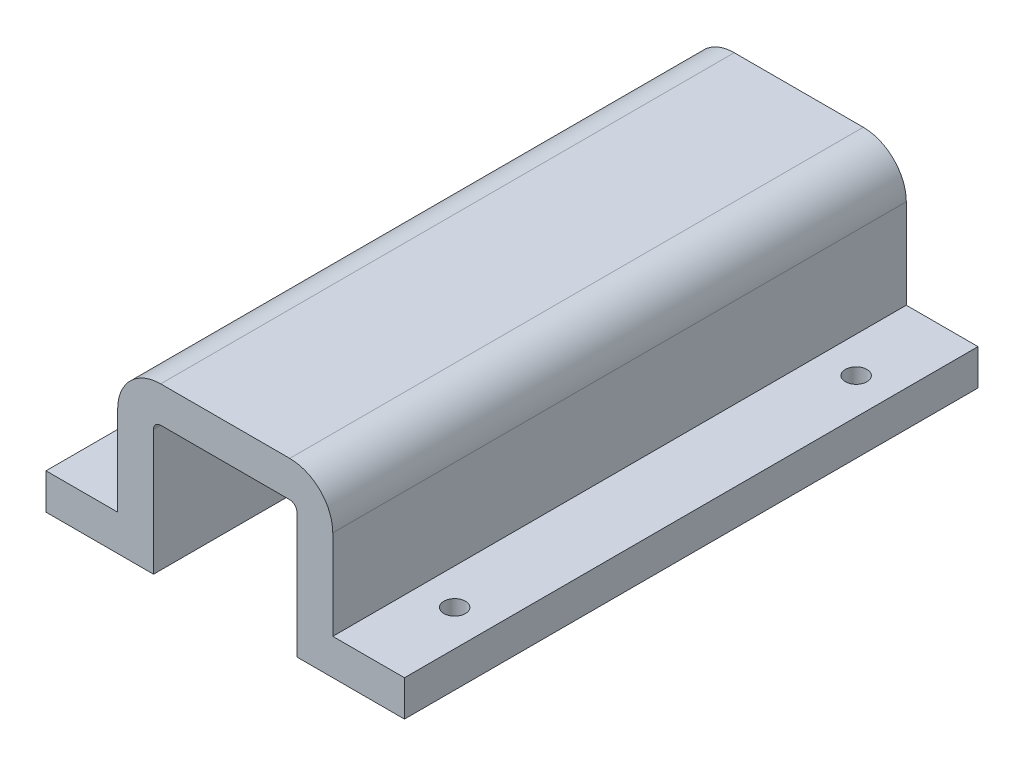
SolidWorks part; units mm, degrees
material "20% infill ABS"
ref_plane "Front" through (0, 0, 0) normal (0, 0, 1) x (1, 0, 0)
ref_plane "Top" through (0, 0, 0) normal (0, 1, 0) x (1, 0, 0)
ref_plane "Right" through (0, 0, 0) normal (1, 0, 0) x (0, 0, -1)
sketch "Sketch1" plane through (0, 0, 0) normal (0, 0, 1) x (1, 0, 0)
  line L0 (9, 15) -> (-9, 15)
  line L1 (-15, 9) -> (-15, -3.5)
  line L3 (15, -3.5) -> (15, 9)
  line L4 (10, -9) -> (10, 9)
  line L5 (9, 10) -> (-9, 10)
  line L6 (-10, 9) -> (-10, -9)
  line L7 (-9, -10) -> (9, -10)
  line L9 (9, 10) -> (-9, 10)
  line L11 (-9, -10) -> (9, -10) construction
  line L12 (-9, -15) -> (9, -15) construction
  line L14 (-15, -3.5) -> (-25, -3.5)
  line L15 (-25, -3.5) -> (-25, -8.5)
  line L16 (-25, -8.5) -> (-10, -8.5)
  line L17 (25, -8.5) -> (25, -3.5)
  line L18 (25, -3.5) -> (15, -3.5)
  line L20 (15, -9) -> (15, 9) construction
  line L21 (-15, 9) -> (-15, -9) construction
  line L22 (10, -9) -> (10, -8.5) construction
  line L23 (-10, -9) -> (-10, -8.5) construction
  line L24 (10, -8.5) -> (25, -8.5)
  line L25 (10, 9) -> (10, -8.5)
  line L26 (-10, 9) -> (-10, -8.5)
  line L29 (-10, 9) -> (-10, -9) construction
  line L30 (10, -9) -> (10, 9) construction
  arc A0 (-9, 15) -> (-15, 9) centre (-9, 9) ccw
  arc A3 (15, 9) -> (9, 15) centre (9, 9) ccw
  arc A4 (9, -10) -> (10, -9) centre (9, -9) ccw
  arc A5 (10, 9) -> (9, 10) centre (9, 9) ccw
  arc A6 (-9, 10) -> (-10, 9) centre (-9, 9) ccw
  arc A7 (-10, -9) -> (-9, -10) centre (-9, -9) ccw
  arc A8 (9, -10) -> (10, -9) centre (9, -9) ccw construction
  arc A9 (10, 9) -> (9, 10) centre (9, 9) ccw
  arc A10 (-9, 10) -> (-10, 9) centre (-9, 9) ccw
  arc A11 (-10, -9) -> (-9, -10) centre (-9, -9) ccw construction
  arc A12 (-15, -9) -> (-9, -15) centre (-9, -9) ccw construction
  arc A13 (9, -15) -> (15, -9) centre (9, -9) ccw construction
  dimension "D3" = 10
  dimension "D4" = 10
  dimension "D5" = 5
  dimension "D6" = 1.5
  dimension "D1" = 0
  dimension "D2" = 5
extrude "Boss-Extrude1" add sketch "Sketch1" along normal blind 80
hole_wizard "Ø3.0mm Dowel Hole1" positions "Sketch2" profile "Sketch3" hole size "Ø3.0" standard "ANSI Metric" end condition through all
sketch "Sketch2" plane through (0, -3.5, 0) normal (0, 1, 0) x (1, 0, 0)
  line L0 (-15, 0) -> (-25, 0) construction
  line L2 (-15, -80) -> (-25, -80) construction
  line L4 (25, -80) -> (15, -80) construction
  line L5 (25, 0) -> (15, 0) construction
  line L6 (15, -80) -> (15, 0) construction
  line L7 (-15, -80) -> (-15, 0) construction
  point P0 (-20, -12)
  point P5 (-20, -68)
  point P7 (20, -12)
  point P9 (20, -68)
  dimension "D1" = 12
  dimension "D2" = 5
  dimension "D3" = 5
  dimension "D4" = 12
  dimension "D5" = 5
  dimension "D6" = 12
  dimension "D7" = 5
  dimension "D8" = 12
sketch "Sketch3" plane through (-20, -3.5, 12) normal (1, 0, 0) x (0, 0, 1)
  line L0 (0, 0) -> (0, 5)
  line L1 (0, 5) -> (1.5, 5)
  line L2 (1.5, 5) -> (1.5, 0)
  line L5 (1.5, 0) -> (0, 0)
  line L11 (0, -6.35) -> (0, 107.95) construction
  dimension "Thru Hole Dia." = 3
  dimension "Thru Hole Depth" = 5
